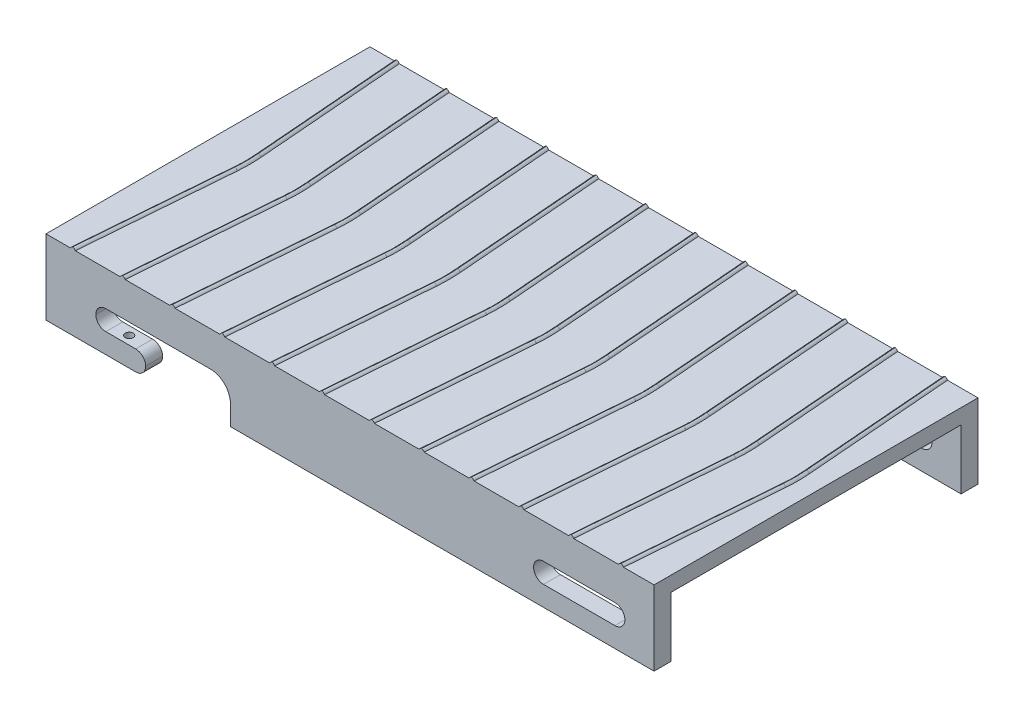
SolidWorks part; units mm, degrees
ref_plane "前基準面" through (0, 0, 0) normal (0, 0, 1) x (1, 0, 0)
ref_plane "上基準面" through (0, 0, 0) normal (0, 1, 0) x (1, 0, 0)
ref_plane "右基準面" through (0, 0, 0) normal (1, 0, 0) x (0, 0, -1)
sketch "草圖1" plane through (0, 0, 0) normal (0, 0, 1) x (1, 0, 0)
  line L1 (0, 0) -> (122, 0)
  line L2 (0, 0) -> (0, 15)
  line L3 (0, 15) -> (122, 15)
  line L4 (122, 0) -> (122, 15)
  dimension "D1" = 15
  dimension "D2" = 122
extrude "填料-伸長1" add sketch "草圖1" along normal blind 4
sketch "草圖2" plane through (0, 0, 4) normal (0, 0, 1) x (1, 0, 0)
  line L0 (99.83, 6) -> (114.15, 6) construction
  line L1 (99.83, 8) -> (114.15, 8)
  line L2 (99.83, 4) -> (114.15, 4)
  line L3 (0, 0) -> (122, 0) construction
  line L4 (122, 0) -> (122, 15) construction
  arc A0 (99.83, 8) -> (99.83, 4) centre (99.83, 6) ccw
  arc A1 (114.15, 4) -> (114.15, 8) centre (114.15, 6) ccw
  point P2 (106.99, 6)
  dimension "D1" = 4
  dimension "D2" = 6
  dimension "D3" = 14.32
  dimension "D4" = 7.85
extrude "除料-伸長1" cut sketch "草圖2" against normal up to next
sketch "草圖3" plane through (0, 0, 4) normal (0, 0, 1) x (1, 0, 0)
  line L0 (20, 0) -> (20, 4)
  line L1 (0, 0) -> (122, 0) construction
  line L2 (20, 4) -> (10, 4)
  line L3 (10, 4) -> (10, 8)
  line L4 (10, 8) -> (37, 8)
  line L5 (37, 8) -> (37, 0)
  line L6 (20, 0) -> (37, 0)
  line L7 (0, 15) -> (0, 0) construction
  dimension "D1" = 4
  dimension "D2" = 4
  dimension "D3" = 10
  dimension "D4" = 20
  dimension "D5" = 17
extrude "除料-伸長2" cut sketch "草圖3" against normal up to next
sketch "草圖4" plane through (0, 0, 4) normal (0, 0, 1) x (1, 0, 0)
  line L0 (122, 0) -> (122, 15) construction
  line L1 (0, 15) -> (122, 15)
  line L2 (0, 15) -> (0, 12)
  line L3 (0, 12) -> (122, 12)
  line L4 (122, 15) -> (122, 12)
  dimension "D1" = 3
extrude "填料-伸長2" add sketch "草圖4" against normal blind 32.5
mirror "鏡射1" about plane through (0, 0, -28.5) normal (0, 0, 1) of bodies 104
fillet "圓角1" radius 2 4 edges at (20, 0, 2) (20, 0, -59) (20, 4, -59) (20, 4, 2)
fillet "圓角2" radius 2 4 edges at (10, 4, -59) (10, 8, -59) (10, 8, 2) (10, 4, 2)
fillet "圓角3" radius 4 2 edges at (37, 8, -59) (37, 8, 2)
sketch "草圖5" plane through (122, 0, 0) normal (1, 0, 0) x (0, 0, -1)
  line L0 (61, 0) -> (57, 0) construction
  line L1 (-0.6, 12) -> (57.6, 12)
  line L2 (-0.6, 12) -> (-0.6, 0)
  line L3 (-0.6, 0) -> (57.6, 0)
  line L4 (57.6, 12) -> (57.6, 0)
  line L5 (28.5, 15) -> (28.5, -12.0699) construction
  line L6 (-4, 15) -> (61, 15) construction
  line L7 (0, 0) -> (0, 12) construction
  dimension "D1" = 0.6
extrude "除料-伸長3" cut sketch "草圖5" against normal through all
sketch "草圖6" plane through (0, 15, 0) normal (0, 1, 0) x (1, 0, 0)
  line L0 (0, 28.5) -> (-35.2041, 28.5) construction
  line L1 (0, -4) -> (0, 61) construction
  line L2 (4.881, 61) -> (7.4671, 28.5)
  line L3 (122, 61) -> (0, 61) construction
  line L4 (7.4671, 28.5) -> (4.881, -4)
  line L5 (5.8841, 61) -> (8.4702, 28.5)
  line L6 (5.8841, -4) -> (8.4702, 28.5)
  line L7 (122, -4) -> (0, -4) construction
  line L9 (122, -4) -> (122, 61)
  line L10 (122, 61) -> (0, 61)
  line L11 (0, 61) -> (0, -4)
  line L12 (0, -4) -> (122, -4)
  line L13 (122, -4) -> (122, 61)
  line L14 (122, 61) -> (0, 61)
  line L15 (0, 61) -> (0, -4)
  line L16 (0, -4) -> (122, -4)
  dimension "D2" = 7.4671
  dimension "D3" = 4.881
  dimension "D4" = 1
  dimension "D1" = 0
extrude "填料-伸長3" add sketch "草圖6" along normal blind 0.5
fillet "圓角4" radius 30 2 edges at (8.4702, 15.25, -28.5) (7.4671, 15.25, -28.5)
fillet "圓角5" radius 1 6 edges at (7.0825, 15.5, -45.9398) (8.3754, 15.5, -28.5) (6.0793, 15.5, -45.9398) (7.3723, 15.5, -28.5) (7.0825, 15.5, -11.0602) (6.0793, 15.5, -11.0602)
pattern_linear "直線複製排列1" count 12 spacing 10 along (1, 0, 0) of "填料-伸長3", "圓角4", "圓角5"
hole_wizard "M2 螺紋孔1" positions "草圖7" profile "草圖8" tap size "M2" standard "ISO"
sketch "草圖7" plane through (0, 0, 0) normal (0, -1, 0) x (-1, 0, 0)
  line L0 (-20, -0.6) -> (-20, -4) construction
  line L1 (-20, -2.3) -> (-15, -2.3) construction
  line L4 (0, 28.5) -> (13.3876, 28.5) construction
  line L5 (0, 57.6) -> (0, -0.6) construction
  point P0 (-15, -2.3)
  point P20 (-15, 59.3)
  dimension "D1" = 5
sketch "草圖8" plane through (15, 0, 2.3) normal (1, 0, 0) x (0, 0, -1)
  line L0 (0, 0) -> (0, 4)
  line L1 (0, 4) -> (0.8, 4)
  line L2 (0.8, 4) -> (0.8, 0)
  line L5 (0.8, 0) -> (0, 0)
  line L11 (0, -6.35) -> (0, 107.95) construction
  dimension "貫穿螺孔鑽直徑" = 1.6
  dimension "貫穿螺孔鑽深度" = 4
cosmetic thread "鑽孔螺紋1" parameters "D2"=2
cosmetic thread "鑽孔螺紋2" parameters "D2"=2
sketch "草圖9" plane through (0, 0, 4) normal (0, 0, 1) x (1, 0, 0)
  line L0 (99.83, 6) -> (114.15, 6)
